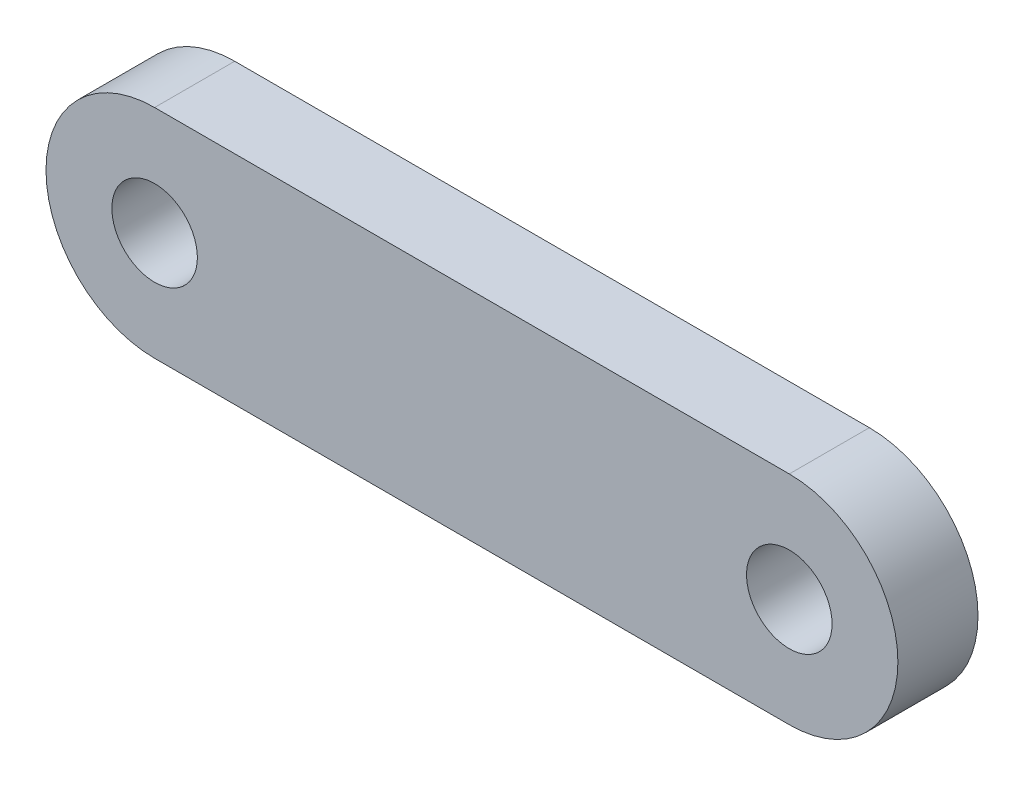
SolidWorks part; units mm, degrees
ref_plane "Front Plane" through (0, 0, 0) normal (0, 0, 1) x (1, 0, 0)
ref_plane "Top Plane" through (0, 0, 0) normal (0, 1, 0) x (1, 0, 0)
ref_plane "Right Plane" through (0, 0, 0) normal (1, 0, 0) x (0, 0, -1)
sketch "Sketch1" plane through (0, 0, 0) normal (0, 0, 1) x (1, 0, 0)
  line L0 (23.375, 0) -> (-23.375, 0) construction
  line L1 (23.375, -8) -> (-23.375, -8)
  line L2 (23.375, 8) -> (-23.375, 8)
  arc A0 (23.375, -8) -> (23.375, 8) centre (23.375, 0) ccw
  arc A1 (-23.375, 8) -> (-23.375, -8) centre (-23.375, 0) ccw
  circle A2 centre (23.375, 0) radius 3.15
  circle A3 centre (-23.375, 0) radius 3.15
  point P2 (0, 0)
  dimension "D2" = 6.3
  dimension "D1" = 16
  dimension "D3" = 46.75
extrude "Boss-Extrude1" add sketch "Sketch1" along normal blind 5.9
